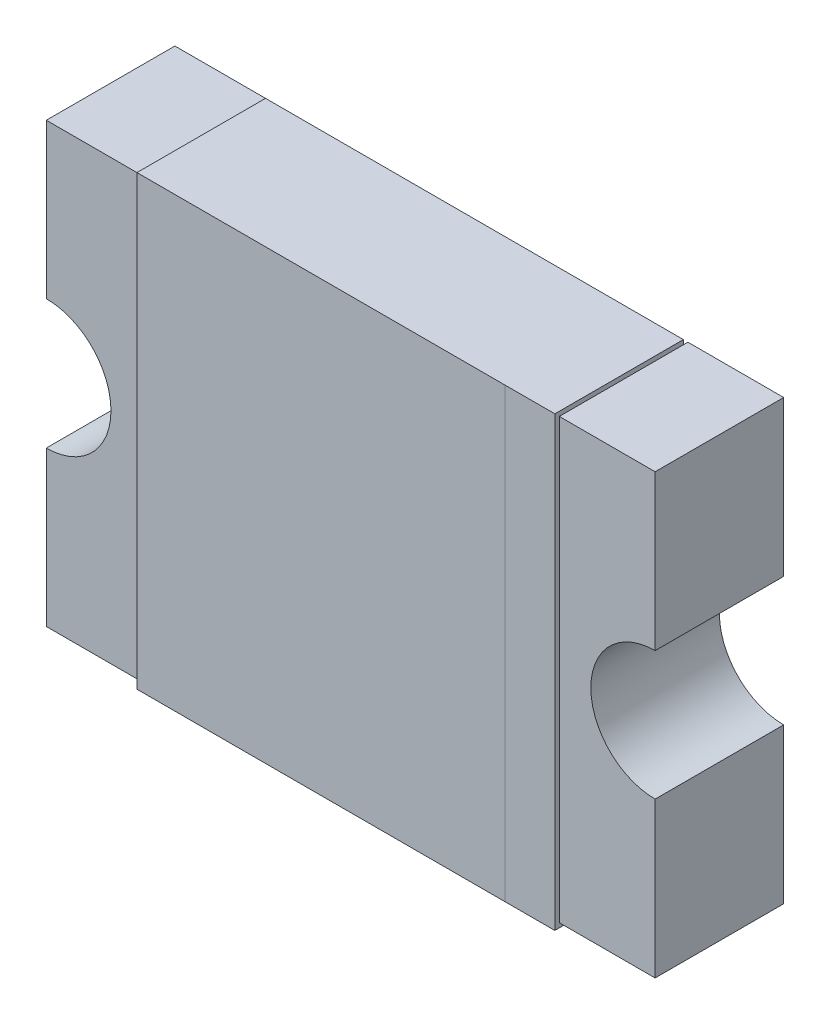
SolidWorks part; units mm, degrees
ref_plane "Plan de face" through (0, 0, 0) normal (0, 0, 1) x (1, 0, 0)
ref_plane "Plan de dessus" through (0, 0, 0) normal (0, 1, 0) x (1, 0, 0)
ref_plane "Plan de droite" through (0, 0, 0) normal (1, 0, 0) x (0, 0, -1)
sketch "Esquisse1" plane through (0, 0, 0) normal (0, 0, 1) x (1, 0, 0)
  line L1 (-2.365, 1.705) -> (2.37, 1.705)
  line L2 (-2.365, 1.705) -> (-2.365, -1.705)
  line L3 (-2.365, -1.705) -> (2.37, -1.705)
  line L4 (2.37, 1.705) -> (2.37, -1.705)
  dimension "D1" = 2.365
  dimension "D2" = 2.37
  dimension "D3" = 1.705
extrude "Extrusion1" add sketch "Esquisse1" along normal blind 1
sketch "Esquisse2" plane through (1.48, 0, 1) normal (0, 0, -1) x (0, 1, 0)
  line L0 (-1.705, 0.89) -> (1.705, 0.89) construction
  circle A0 centre (0, 0.89) radius 0.5
extrude "Enlèv. mat.-Extru.1" cut sketch "Esquisse2" along normal up to vertex (1 mm away) up to point (2.37, -1.705, 0)
sketch "Esquisse4" plane through (0, 0, 1) normal (0, 0, 1) x (1, 0, 0)
  line L0 (-2.365, 1.705) -> (-2.365, -1.705) construction
  circle A0 centre (-2.365, 0) radius 0.5029
extrude "Enlèv. mat.-Extru.2" cut sketch "Esquisse4" against normal up to vertex (1 mm away) up to point (-2.365, 1.705, 0)
sketch "Esquisse8" plane through (0, 0, 1) normal (0, 0, 1) x (1, 0, 0)
  line L0 (2.37, 1.705) -> (-2.365, 1.705) construction
  line L1 (1.625, 1.705) -> (-1.625, 1.705)
  line L2 (1.625, 1.705) -> (1.625, -1.705)
  line L3 (1.625, -1.705) -> (-1.625, -1.705)
  line L4 (-1.625, 1.705) -> (-1.625, -1.705)
  line L5 (-2.365, -1.705) -> (2.37, -1.705) construction
  dimension "D1" = 1.625
  dimension "D2" = 3.25
extrude "Extrusion3" add sketch "Esquisse8" along normal blind 0.035
sketch "Esquisse10" plane through (0, 1.705, 0) normal (0, 1, 0) x (-1, 0, 0)
  line L0 (-2.37, 0) -> (2.365, 0) construction
  line L1 (1.625, 1.035) -> (-1.625, 1.035)
  line L2 (1.625, 1.035) -> (1.625, 0)
  line L3 (1.625, 0) -> (-1.625, 0)
  line L4 (-1.625, 1.035) -> (-1.625, 0)
extrude "Extrusion5" add sketch "Esquisse10" along normal blind 0.035
sketch "Esquisse11" plane through (0, -1.705, 0) normal (0, -1, 0) x (1, 0, 0)
  line L0 (-2.365, 0) -> (2.37, 0) construction
  line L1 (-1.625, 1.035) -> (1.625, 1.035)
  line L2 (-1.625, 1.035) -> (-1.625, 0)
  line L3 (-1.625, 0) -> (1.625, 0)
  line L4 (1.625, 1.035) -> (1.625, 0)
extrude "Extrusion6" add sketch "Esquisse11" along normal blind 0.035
sketch "Esquisse12" plane through (0, 0, 0) normal (0, 0, -1) x (1, 0, 0)
  line L1 (-1.625, 1.74) -> (1.625, 1.74)
  line L2 (-1.625, 1.74) -> (-1.625, -1.74)
  line L3 (-1.625, -1.74) -> (1.625, -1.74)
  line L4 (1.625, 1.74) -> (1.625, -1.74)
extrude "Enlèv. mat.-Extru.6" cut sketch "Esquisse12" against normal blind 0.035
sketch "Esquisse13" plane through (0, 0, 1.035) normal (0, 0, 1) x (1, 0, 0)
  line L0 (1.625, -1.74) -> (-1.625, -1.74) construction
  line L1 (1.625, 1.74) -> (1.2369, 1.74)
  line L2 (1.625, 1.74) -> (1.625, -1.74)
  line L3 (1.625, -1.74) -> (1.2369, -1.74)
  line L4 (1.2369, 1.74) -> (1.2369, -1.74)
extrude "Enlèv. mat.-Extru.7" cut sketch "Esquisse13" against normal blind 0.0001
